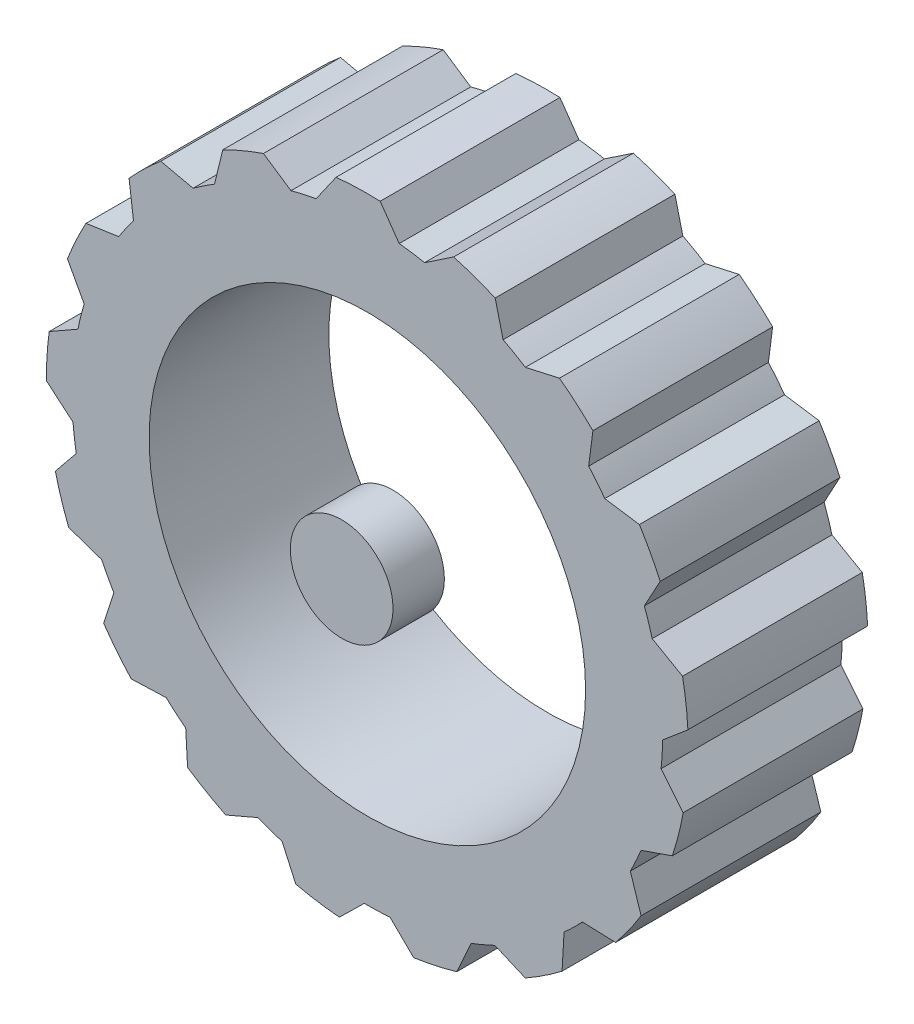
SolidWorks part; units mm, degrees
ref_plane "Front Plane" through (0, 0, 0) normal (0, 0, 1) x (1, 0, 0)
ref_plane "Top Plane" through (0, 0, 0) normal (0, 1, 0) x (1, 0, 0)
ref_plane "Right Plane" through (0, 0, 0) normal (1, 0, 0) x (0, 0, -1)
sketch "Sketch2" plane through (0, 0, 0) normal (0, 0, 1) x (1, 0, 0)
  line L0 (0, 0) -> (0, 62.5) construction
  line L1 (0, 0) -> (62.5, 0) construction
  line L2 (2.5, 62.45) -> (6.2008, 57.1647)
  line L3 (11.1435, 56.4099) -> (16.7998, 60.1998)
  line L4 (30.7686, 48.5751) -> (37.412, 50.0658)
  line L5 (24.8907, 57.3298) -> (26.4323, 51.0645)
  line L6 (46.2382, 34.1801) -> (52.9716, 33.1702)
  line L7 (43.9198, 44.4669) -> (43.094, 38.0677)
  line L8 (55.4631, 15.1688) -> (61.377, 11.7948)
  line L9 (57.0173, 25.5984) -> (53.9357, 19.9297)
  line L10 (57.1974, -5.8911) -> (61.4931, -11.1736)
  line L11 (62.4143, 3.2728) -> (57.493, -0.8999)
  line L12 (51.2069, -26.1554) -> (53.3042, -32.633)
  line L13 (59.3818, -19.4948) -> (53.2855, -21.608)
  line L14 (38.3006, -42.8872) -> (37.9163, -49.685)
  line L15 (48.3296, -39.6296) -> (41.8816, -39.3978)
  line L16 (20.2216, -53.8269) -> (17.4076, -60.0269)
  line L17 (30.7501, -54.4121) -> (24.8213, -51.8667)
  line L18 (-0.5885, -57.497) -> (-5.4521, -62.2617)
  line L19 (9.0177, -61.846) -> (4.4088, -57.3307)
  line L20 (-21.3191, -53.4018) -> (-27.5755, -56.0878)
  line L21 (-13.9326, -60.9273) -> (-16.5992, -55.0519)
  line L22 (-39.1704, -42.0943) -> (-45.9746, -42.3389)
  line L23 (-35.0012, -51.78) -> (-35.3654, -45.3381)
  line L24 (-51.7315, -25.1018) -> (-58.1646, -22.8719)
  line L25 (-51.3427, -35.6395) -> (-49.3552, -29.5011)
  line L26 (-57.306, -4.7192) -> (-62.4992, -0.316)
  line L27 (-60.7501, -14.6857) -> (-56.6794, -9.6798)
  line L28 (-55.141, 16.3008) -> (-58.3929, 22.2827)
  line L29 (-61.9529, 8.2515) -> (-56.3487, 11.4489)
  line L30 (-45.5289, 35.1193) -> (-46.4003, 41.8719)
  line L31 (-54.7886, 30.0743) -> (-48.4078, 31.0312)
  line L32 (-29.7679, 49.1947) -> (-28.1411, 55.8062)
  line L33 (-40.2248, 47.8353) -> (-33.9291, 46.4227)
  line L34 (-9.9866, 56.6261) -> (-6.0813, 62.2034)
  line L35 (-20.2284, 59.136) -> (-14.8682, 55.5445)
  arc A0 (-20.2284, 59.136) -> (-28.1411, 55.8062) centre (0, 0) ccw
  circle A1 centre (0, 0) radius 42.5
  arc A2 (-9.9866, 56.6261) -> (-14.8682, 55.5445) centre (0, 0) ccw
  arc A3 (-6.0813, 62.2034) -> (-20.2284, 59.136) centre (0, 0) ccw construction
  arc A4 (0, 57.5) -> (-9.9866, 56.6261) centre (0, 0) ccw construction
  arc A5 (6.2008, 57.1647) -> (0, 57.5) centre (0, 0) ccw construction
  arc A6 (16.7998, 60.1998) -> (2.5, 62.45) centre (0, 0) ccw construction
  arc A7 (2.5, 62.45) -> (-6.0813, 62.2034) centre (0, 0) ccw
  arc A8 (26.4323, 51.0645) -> (11.1435, 56.4099) centre (0, 0) ccw construction
  arc A9 (11.1435, 56.4099) -> (6.2008, 57.1647) centre (0, 0) ccw
  arc A10 (37.412, 50.0658) -> (24.8907, 57.3298) centre (0, 0) ccw construction
  arc A11 (24.8907, 57.3298) -> (16.7998, 60.1998) centre (0, 0) ccw
  arc A12 (43.094, 38.0677) -> (30.7686, 48.5751) centre (0, 0) ccw construction
  arc A13 (30.7686, 48.5751) -> (26.4323, 51.0645) centre (0, 0) ccw
  arc A14 (52.9716, 33.1702) -> (43.9198, 44.4669) centre (0, 0) ccw construction
  arc A15 (43.9198, 44.4669) -> (37.412, 50.0658) centre (0, 0) ccw
  arc A16 (53.9357, 19.9297) -> (46.2382, 34.1801) centre (0, 0) ccw construction
  arc A17 (46.2382, 34.1801) -> (43.094, 38.0677) centre (0, 0) ccw
  arc A18 (61.377, 11.7948) -> (57.0173, 25.5984) centre (0, 0) ccw construction
  arc A19 (57.0173, 25.5984) -> (52.9716, 33.1702) centre (0, 0) ccw
  arc A20 (57.5, 0) -> (55.4631, 15.1688) centre (0, 0) ccw construction
  arc A21 (55.4631, 15.1688) -> (53.9357, 19.9297) centre (0, 0) ccw
  arc A22 (61.4931, -11.1736) -> (62.5, 0) centre (0, 0) ccw construction
  arc A23 (62.4143, 3.2728) -> (61.377, 11.7948) centre (0, 0) ccw
  arc A24 (62.5, 0) -> (62.4143, 3.2728) centre (0, 0) ccw construction
  arc A25 (53.2855, -21.608) -> (57.1974, -5.8911) centre (0, 0) ccw construction
  arc A26 (57.1974, -5.8911) -> (57.493, -0.8999) centre (0, 0) ccw
  arc A27 (53.3042, -32.633) -> (59.3818, -19.4948) centre (0, 0) ccw construction
  arc A28 (59.3818, -19.4948) -> (61.4931, -11.1736) centre (0, 0) ccw
  arc A29 (41.8816, -39.3978) -> (51.2069, -26.1554) centre (0, 0) ccw construction
  arc A30 (51.2069, -26.1554) -> (53.2855, -21.608) centre (0, 0) ccw
  arc A31 (57.493, -0.8999) -> (57.5, 0) centre (0, 0) ccw construction
  arc A32 (37.9163, -49.685) -> (48.3296, -39.6296) centre (0, 0) ccw construction
  arc A33 (48.3296, -39.6296) -> (53.3042, -32.633) centre (0, 0) ccw
  arc A34 (24.8213, -51.8667) -> (38.3006, -42.8872) centre (0, 0) ccw construction
  arc A35 (38.3006, -42.8872) -> (41.8816, -39.3978) centre (0, 0) ccw
  arc A36 (17.4076, -60.0269) -> (30.7501, -54.4121) centre (0, 0) ccw construction
  arc A37 (30.7501, -54.4121) -> (37.9163, -49.685) centre (0, 0) ccw
  arc A38 (4.4088, -57.3307) -> (20.2216, -53.8269) centre (0, 0) ccw construction
  arc A39 (20.2216, -53.8269) -> (24.8213, -51.8667) centre (0, 0) ccw
  arc A40 (-5.4521, -62.2617) -> (9.0177, -61.846) centre (0, 0) ccw construction
  arc A41 (9.0177, -61.846) -> (17.4076, -60.0269) centre (0, 0) ccw
  arc A42 (-16.5992, -55.0519) -> (-0.5885, -57.497) centre (0, 0) ccw construction
  arc A43 (-0.5885, -57.497) -> (4.4088, -57.3307) centre (0, 0) ccw
  arc A44 (-27.5755, -56.0878) -> (-13.9326, -60.9273) centre (0, 0) ccw construction
  arc A45 (-13.9326, -60.9273) -> (-5.4521, -62.2617) centre (0, 0) ccw
  arc A46 (-35.3654, -45.3381) -> (-21.3191, -53.4018) centre (0, 0) ccw construction
  arc A47 (-21.3191, -53.4018) -> (-16.5992, -55.0519) centre (0, 0) ccw
  arc A48 (-45.9746, -42.3389) -> (-35.0012, -51.78) centre (0, 0) ccw construction
  arc A49 (-35.0012, -51.78) -> (-27.5755, -56.0878) centre (0, 0) ccw
  arc A50 (-49.3552, -29.5011) -> (-39.1704, -42.0943) centre (0, 0) ccw construction
  arc A51 (-39.1704, -42.0943) -> (-35.3654, -45.3381) centre (0, 0) ccw
  arc A52 (-58.1646, -22.8719) -> (-51.3427, -35.6395) centre (0, 0) ccw construction
  arc A53 (-51.3427, -35.6395) -> (-45.9746, -42.3389) centre (0, 0) ccw
  arc A54 (-56.6794, -9.6798) -> (-51.7315, -25.1018) centre (0, 0) ccw construction
  arc A55 (-51.7315, -25.1018) -> (-49.3552, -29.5011) centre (0, 0) ccw
  arc A56 (-62.4992, -0.316) -> (-60.7501, -14.6857) centre (0, 0) ccw construction
  arc A57 (-60.7501, -14.6857) -> (-58.1646, -22.8719) centre (0, 0) ccw
  arc A58 (-56.3487, 11.4489) -> (-57.306, -4.7192) centre (0, 0) ccw construction
  arc A59 (-57.306, -4.7192) -> (-56.6794, -9.6798) centre (0, 0) ccw
  arc A60 (-58.3929, 22.2827) -> (-61.9529, 8.2515) centre (0, 0) ccw construction
  arc A61 (-61.9529, 8.2515) -> (-62.4992, -0.316) centre (0, 0) ccw
  arc A62 (-48.4078, 31.0312) -> (-55.141, 16.3008) centre (0, 0) ccw construction
  arc A63 (-55.141, 16.3008) -> (-56.3487, 11.4489) centre (0, 0) ccw
  arc A64 (-46.4003, 41.8719) -> (-54.7886, 30.0743) centre (0, 0) ccw construction
  arc A65 (-54.7886, 30.0743) -> (-58.3929, 22.2827) centre (0, 0) ccw
  arc A66 (-33.9291, 46.4227) -> (-45.5289, 35.1193) centre (0, 0) ccw construction
  arc A67 (-45.5289, 35.1193) -> (-48.4078, 31.0312) centre (0, 0) ccw
  arc A68 (-28.1411, 55.8062) -> (-40.2248, 47.8353) centre (0, 0) ccw construction
  arc A69 (-40.2248, 47.8353) -> (-46.4003, 41.8719) centre (0, 0) ccw
  arc A70 (-14.8682, 55.5445) -> (-29.7679, 49.1947) centre (0, 0) ccw construction
  arc A71 (-29.7679, 49.1947) -> (-33.9291, 46.4227) centre (0, 0) ccw
  dimension "D1" = 125
  dimension "D2" = 20
  dimension "D3" = 5
  dimension "D4" = 5
  dimension "D5" = 2.5
  dimension "D7" = 55
  dimension "D8" = 55
  dimension "D6" = 17
extrude "Boss-Extrude1" add sketch "Sketch2" against normal blind 35
sketch "Sketch3" plane through (0, 0, 0) normal (0, 0, 1) x (1, 0, 0)
  circle A0 centre (0, 0) radius 10
  dimension "D1" = 20
extrude "Boss-Extrude2" add sketch "Sketch3" along normal mid plane 10 separate body
